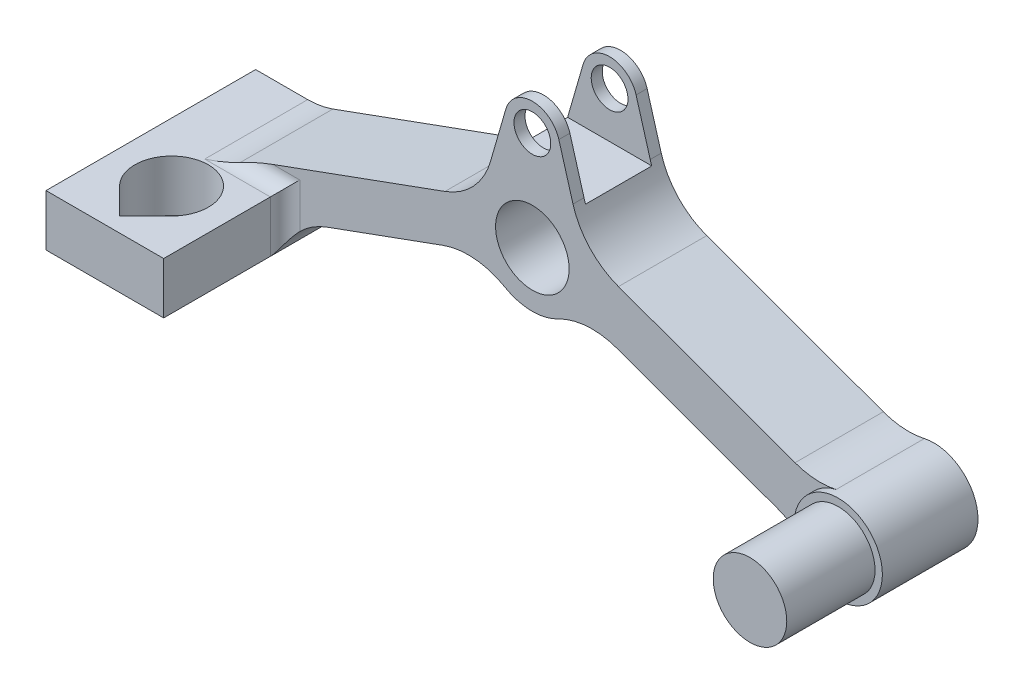
SolidWorks part; units mm, degrees
ref_plane "Alzado" through (0, 0, 0) normal (0, 0, 1) x (1, 0, 0)
ref_plane "Planta" through (0, 0, 0) normal (0, 1, 0) x (1, 0, 0)
ref_plane "Vista lateral" through (0, 0, 0) normal (1, 0, 0) x (0, 0, -1)
sketch "Croquis1" plane through (0, 0, 0) normal (0, 0, 1) x (1, 0, 0)
  line L0 (0, 0) -> (0, 13.5) construction
  line L1 (-3.6024, 14.5417) -> (-7.2048, 2.0833)
  line L2 (3.6024, 14.5417) -> (7.2048, 2.0833)
  circle A0 centre (0, 0) radius 5
  arc A1 (-7.2048, 2.0833) -> (7.2048, 2.0833) centre (0, 0) ccw
  circle A2 centre (0, 13.5) radius 2.5
  arc A3 (3.6024, 14.5417) -> (-3.6024, 14.5417) centre (0, 13.5) ccw
  dimension "D1" = 10
  dimension "D2" = 15
  dimension "D4" = 5
  dimension "D5" = 7.5
  dimension "D3" = 13.5
extrude "Saliente-Extruir1" add sketch "Croquis1" along normal mid plane 12
sketch "Croquis3" plane through (0, 0, 0) normal (1, 0, 0) x (0, 0, -1)
  line L0 (-4.5, 21.4548) -> (-4.5, 7.25)
  line L1 (-4.5, 7.25) -> (4.5, 7.25)
  line L2 (4.5, 7.25) -> (4.5, 21.4548)
  line L3 (4.5, 21.4548) -> (-4.5, 21.4548)
  line L4 (0, 0) -> (0, 21.4548) construction
  line L5 (6, 17.25) -> (-6, 17.25) construction
  line L6 (6, 2.0833) -> (6, 14.5417) construction
  point P7 (0, 21.4548)
  dimension "D1" = 9
  dimension "D2" = 10
extrude "Cortar-Extruir1" cut sketch "Croquis3" against normal through all both and the other way through all
sketch3d "Croquis3D1"
  line L0 (-5, 0, 0) -> (-41.6243, -13.3302, 0) construction
  line L1 (-41.6243, -13.3302, 0) -> (-41.6243, -13.3302, 8.998) construction
  line L2 (-41.6243, -13.3302, 8.998) -> (-5, 0, 0) construction
  line L3 (-5, 0, 0) -> (-41.6243, 0, 0) construction
  line L4 (-41.6243, 0, 0) -> (-41.6243, -13.3302, 0) construction
  line L5 (0, 0, 0) -> (-5, 0, 0) construction
  line L6 (-41.6243, -13.3302, 8.998) -> (-41.6243, -7.3302, 8.998) construction
  line L7 (0, 0, 0) -> (5, 0, 0) construction
  line L8 (5, 0, 0) -> (42.5877, -13.6808, 0) construction
  line L9 (5, 0, 0) -> (42.5877, 0, 0) construction
  line L10 (42.5877, 0, 0) -> (42.5877, -13.6808, 0) construction
  dimension "D1" = 40
  dimension "D2" = 13
  dimension "D3" = 20
  dimension "D4" = 5
  dimension "D5" = 6
  dimension "D6" = 5
  dimension "D7" = 20
  dimension "D8" = 40
ref_plane "Plano1" through (-41.6243, -13.3302, 0) normal (-0.9397, -0.342, 0) x (0, 0, 1)
sketch "Croquis4" plane through (-41.6243, -13.3302, 0) normal (-0.9397, -0.342, 0) x (0, 0, 1)
  line L1 (-6, 3) -> (6, 3)
  line L2 (-6, 3) -> (-6, -3)
  line L3 (-6, -3) -> (6, -3)
  line L4 (6, 3) -> (6, -3)
  line L5 (-6, 3) -> (6, -3) construction
  line L6 (-6, -3) -> (6, 3) construction
  point P0 (0, 0)
  dimension "D2" = 6
  dimension "D3" = 12
extrude "Saliente-Extruir2" add sketch "Croquis4" against normal blind 38
ref_plane "Plano2" through (-41.6243, -7.3302, 8.998) normal (0, 1, 0) x (1, 0, 0)
ref_plane "Plano3" through (42.5877, -13.6808, 0) normal (0.9397, -0.342, 0) x (0, 0, -1)
sketch "Croquis8" plane through (42.5877, -13.6808, 0) normal (0.9397, -0.342, 0) x (0, 0, -1)
  line L1 (-6, 3.5) -> (6, 3.5)
  line L2 (-6, 3.5) -> (-6, -3.5)
  line L3 (-6, -3.5) -> (6, -3.5)
  line L4 (6, 3.5) -> (6, -3.5)
  line L5 (-6, 3.5) -> (6, -3.5) construction
  line L6 (-6, -3.5) -> (6, 3.5) construction
  point P1 (0, 0)
  dimension "D1" = 12
  dimension "D2" = 7
extrude "Saliente-Extruir5" add sketch "Croquis8" against normal blind 39.5
sketch "Croquis9" plane through (0, 0, 0) normal (0, 0, 1) x (1, 0, 0)
  circle A0 centre (42.5877, -13.6808) radius 5
  dimension "D1" = 10
extrude "Saliente-Extruir6" add sketch "Croquis9" along normal blind 19
sketch "Croquis11" plane through (0, 0, 0) normal (0, 0, -1) x (-1, 0, 0)
  line L1 (-5, 0) -> (-42.5877, -13.6808) construction
  line L2 (-42.5877, 0) -> (-42.5877, -13.6808) construction
  circle A0 centre (-42.5877, -13.6808) radius 6
  dimension "D1" = 12
extrude "Saliente-Extruir7" add sketch "Croquis11" along normal mid plane 12
sketch "Croquis22" plane through (0, 0, -6) normal (0, 0, -1) x (-1, 0, 0)
  line L1 (33.6243, -16.8302) -> (49.6243, -16.8302)
  line L2 (33.6243, -16.8302) -> (33.6243, -9.8302)
  line L3 (33.6243, -9.8302) -> (49.6243, -9.8302)
  line L4 (49.6243, -16.8302) -> (49.6243, -9.8302)
  line L5 (33.6243, -16.8302) -> (49.6243, -9.8302) construction
  line L6 (33.6243, -9.8302) -> (49.6243, -16.8302) construction
  point P0 (41.6243, -13.3302)
  dimension "D1" = 7
  dimension "D2" = 16
extrude "Saliente-Extruir12" add sketch "Croquis22" against normal blind 28.5
sketch "Croquis24" plane through (0, -16.8302, 0) normal (0, -1, 0) x (1, 0, 0)
  line L0 (-41.6243, 13.4289) -> (-41.6243, 20.5) construction
  line L1 (-41.6243, 20.5) -> (-45.1599, 16.9645)
  line L2 (-41.6243, 20.5) -> (-38.0888, 16.9645)
  line L3 (-41.6243, 13.4289) -> (-41.6243, 22.5) construction
  line L4 (-33.6243, 22.5) -> (-49.6243, 22.5) construction
  arc A0 (-45.1599, 16.9645) -> (-38.0888, 16.9645) centre (-41.6243, 13.4289) ccw
  dimension "D1" = 10
  dimension "D2" = 90
  dimension "D3" = 2
extrude "Cortar-Extruir3" cut sketch "Croquis24" against normal blind 17
fillet "Redondeo1" radius 10 4 edges at (-6.5015, -3.739, 0) (6.2319, -4.173, 0) (6.9338, 3.0208, 0) (-7.1057, 2.4261, 0)
fillet "Redondeo2" radius 10 4 edges at (-33.6243, -13.6109, 0) (-40.7796, -9.8302, 0) (36.8111, -15.3029, 0) (39.2053, -8.7251, 0)
fillet "Redondeo3" radius 2 2 edges at (-33.6243, -13.3302, 6) (-38.0836, -9.8302, 6)
sketch "Croquis25" plane through (0, 0, 6) normal (0, 0, 1) x (1, 0, 0)
  circle A0 centre (42.5877, -13.6808) radius 6
extrude "Saliente-Extruir13" add sketch "Croquis25" along normal blind 1
